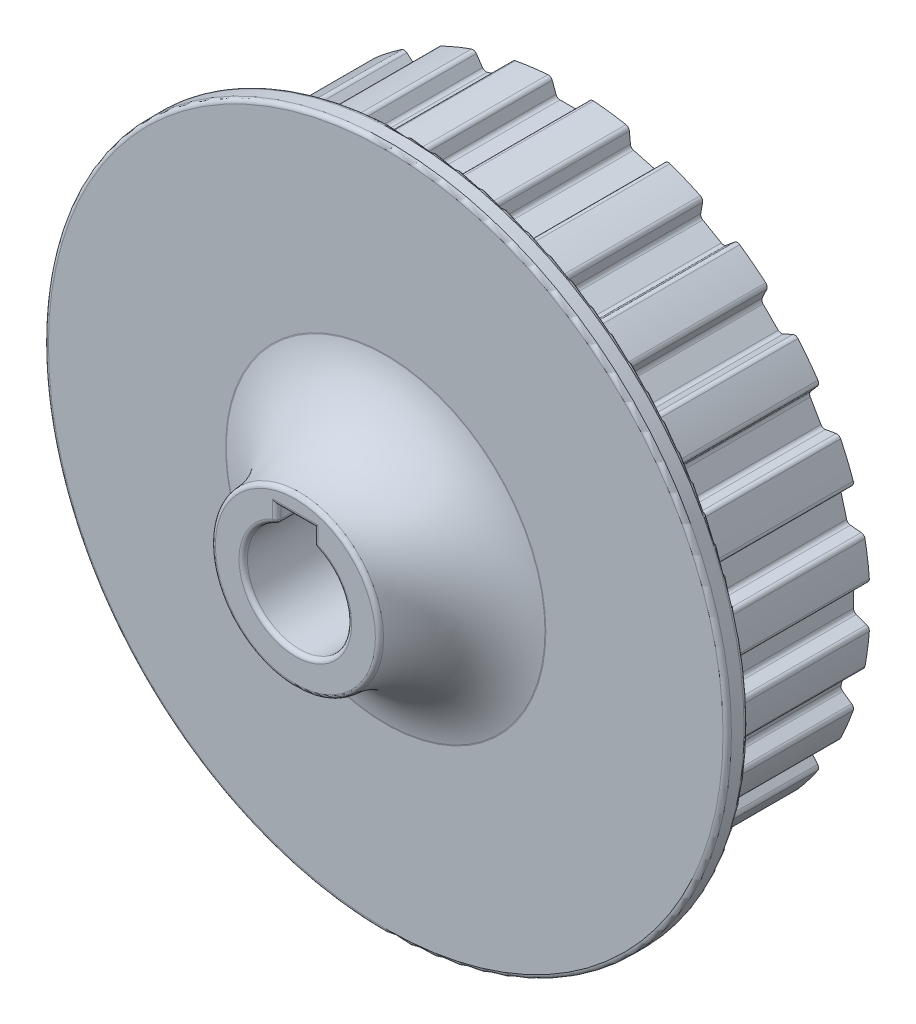
SolidWorks part; units mm, degrees
ref_plane "Front Plane" through (0, 0, 0) normal (0, 0, 1) x (1, 0, 0)
ref_plane "Top Plane" through (0, 0, 0) normal (0, 1, 0) x (1, 0, 0)
ref_plane "Right Plane" through (0, 0, 0) normal (1, 0, 0) x (0, 0, -1)
sketch "Sketch1" plane through (0, 0, 0) normal (0, 1, 0) x (1, 0, 0)
  line L0 (0, 36.1296) -> (0, -19.4741) construction
sketch "Sketch7" plane through (0, 0, 0) normal (0, 0, 1) x (1, 0, 0)
  line L0 (0, 0) -> (0, 34.591) construction
  line L1 (-2.325, 35.546) -> (-2.9401, 37.236) construction
  line L2 (-2.325, 35.546) -> (-1.6298, 33.636) construction
  line L3 (-1.6298, 33.636) -> (1.6298, 33.636) construction
  line L4 (1.6298, 33.636) -> (2.325, 35.546) construction
  line L5 (2.325, 35.546) -> (-2.325, 35.546) construction
  line L6 (0, 33.636) -> (0, 35.546) construction
  line L7 (2.325, 35.546) -> (2.9401, 37.236) construction
  line L8 (-2.9401, 37.236) -> (2.9401, 37.236) construction
  line L9 (0, 0) -> (8.9528, 33.4123) construction
  line L10 (8.9528, 33.4123) -> (9.2196, 34.4082) construction
  line L11 (0, 35.546) -> (0, 35.622) construction
  line L12 (0, 35.622) -> (0, 37.3519) construction
  line L13 (0, 36.4869) -> (9.4435, 35.2437) construction
  line L14 (9.2196, 34.4082) -> (9.6674, 36.0792) construction
  circle A1 centre (0, 0) radius 34.591 construction
  circle A2 centre (-1.2727, 34.146) radius 0.51 construction
  circle A3 centre (1.2727, 34.146) radius 0.51 construction
  circle A4 centre (0, 0) radius 35.622
  circle A5 centre (0, 0) radius 37.3519 construction
  dimension "D3" = 40
  dimension "D6" = 1.02
  dimension "D1" = 3.6
  dimension "D2" = 15
  dimension "D7" = 9.525
  dimension "D4" = 1.91
  dimension "D5" = 4.65
extrude "Boss-Extrude1" add sketch "Sketch7" along normal blind 7.25 and the other way blind 7.25 contours A4 region at (0, 0, 0)
sketch "Sketch14" plane through (0, 0, 0) normal (1, 0, 0) x (0, 0, -1)
  line L0 (-18, 0) -> (-18, 10)
  line L1 (-18, 0) -> (0, 0)
  line L2 (0, 0) -> (0, 19)
  line L3 (0, 19) -> (-7.25, 19)
  line L4 (-7.25, 19) -> (-18, 10)
  line L5 (-7.25, 35.622) -> (-7.25, -35.622) construction
  line L6 (-18, 6.7395) -> (-3.3555, 19) construction
  arc A0 (-7.25, 19) -> (-18, 10) centre (-18.1316, 21.0773) cw
  dimension "D1" = 10
  dimension "D2" = 19
  dimension "D3" = 18
  dimension "D4" = 2.5
revolve "Revolve1" add sketch "Sketch14" angle 360 about L0 region at (0, 7.5733, 7.5341) region at (0, 9.2725, 16.1663) region at (0, 17.2765, 6.6188)
sketch "Sketch9" plane through (0, 0, 0) normal (0, 0, 1) x (1, 0, 0)
  line L0 (2, 0) -> (-2, 0) construction
  line L1 (-2, 0) -> (-2, 7.5) construction
  line L2 (-2, 7.5) -> (2, 7.5) construction
  line L3 (2, 7.5) -> (2, 0) construction
  circle A0 centre (0, 0) radius 6 construction
  dimension "D1" = 12
  dimension "D2" = 4
  dimension "D3" = 7.5
sketch "Sketch10" plane through (0, 0, 0) normal (0, 0, 1) x (1, 0, 0)
  line L0 (2, 0) -> (-2, 0) construction
  line L1 (-2.2, 7.7) -> (2.2, 7.7)
  line L2 (-2.2, 7.7) -> (-2.2, 0)
  line L3 (-2.2, 0) -> (2.2, 0)
  line L4 (2.2, 7.7) -> (2.2, 0)
  line L5 (-2, 7.5) -> (2, 7.5) construction
  line L6 (2, 7.5) -> (2, 0) construction
  circle A0 centre (0, 0) radius 6.2
  circle A1 centre (0, 0) radius 6 construction
  dimension "D1" = 0.2
  dimension "D2" = 0.2
  dimension "D3" = 0.2
extrude "Cut-Extrude3" cut sketch "Sketch10" against normal through all both and the other way through all contours A0 L4 L1 L2 | L2 A0 L4 L3 | L4 A0 L2 L3 region at (0, 6.8793, 0) region at (0, 3.0348, 0) region at (0, -0.8613, 0)
sketch "Sketch11" [suppressed] plane through (0, 0, 0) normal (0, 1, 0) x (1, 0, 0)
  line L0 (29.5757, 7.25) -> (-29.5757, 7.25) construction
  line L1 (11, 7.25) -> (17.5, 7.25)
  line L2 (11, 7.25) -> (11, 4.75)
  line L3 (11, 4.75) -> (17.5, 4.75)
  line L4 (17.5, 7.25) -> (17.5, 4.75)
  line L5 (-29.5757, -7.25) -> (29.5757, -7.25) construction
  line L6 (11, -7.25) -> (17.5, -7.25)
  line L7 (11, -7.25) -> (11, -4.75)
  line L8 (11, -4.75) -> (17.5, -4.75)
  line L9 (17.5, -7.25) -> (17.5, -4.75)
  line L11 (11, 4.75) -> (11, -4.75) construction
  line L12 (17.5, -4.75) -> (17.5, 4.75) construction
  line L13 (6.2, 7.25) -> (-6.2, 7.25) construction
  line L14 (0, 7.25) -> (22.5, 7.25)
  line L15 (0, 7.25) -> (0, -7.25)
  line L16 (0, -7.25) -> (22.5, -7.25)
  line L17 (22.5, 7.25) -> (22.5, -7.25)
  line L18 (-6.2, -7.25) -> (6.2, -7.25) construction
  line L19 (6, 7.25) -> (6, -7.25) construction
  dimension "D1" = 22.5
  dimension "D2" = 6
  dimension "D3" = 5
  dimension "D4" = 5
  dimension "D5" = 2.5
sketch "Sketch15" plane through (0, 0, -7.25) normal (0, 0, -1) x (-1, 0, 0)
  circle A0 centre (0, 0) radius 8.0081
  circle A1 centre (0, 0) radius 2.25
  dimension "D1" = 4.5
extrude "Boss-Extrude2" add sketch "Sketch15" against normal blind 5.5
sketch "Sketch16" plane through (0, 0, -7.25) normal (0, 0, -1) x (-1, 0, 0)
  circle A0 centre (0, 0) radius 5
  dimension "D1" = 10
extrude "Cut-Extrude4" cut sketch "Sketch16" against normal blind 3
sketch "Sketch17" plane through (0, 0, -7.25) normal (0, 0, -1) x (-1, 0, 0)
  circle A0 centre (0, 0) radius 35.622
  circle A1 centre (0, 0) radius 35.622 construction
  circle A2 centre (0, 0) radius 5
  circle A3 centre (0, 0) radius 5 construction
extrude "Boss-Extrude3" add sketch "Sketch17" along normal blind 7.5
sketch "Sketch8" plane through (0, 0, 0) normal (0, 0, 1) x (1, 0, 0)
  line L6 (-1.6298, 33.636) -> (-2.3526, 35.622)
  line L7 (-2.3526, 35.622) -> (2.3526, 35.622)
  line L8 (2.3526, 35.622) -> (1.6298, 33.636)
  line L9 (1.6298, 33.636) -> (-1.6298, 33.636)
  line L10 (-2.325, 35.546) -> (-1.6298, 33.636) construction
  line L11 (1.6298, 33.636) -> (2.325, 35.546) construction
  line L12 (7.1314, 32.9117) -> (6.9472, 35.0171)
  line L13 (6.9472, 35.0171) -> (11.4921, 33.7993)
  line L14 (11.4921, 33.7993) -> (10.2799, 32.0681)
  line L15 (10.2799, 32.0681) -> (7.1314, 32.9117)
  line L16 (15.4065, 29.9445) -> (15.7735, 32.0258)
  line L17 (15.7735, 32.0258) -> (19.8484, 29.6732)
  line L18 (19.8484, 29.6732) -> (18.2295, 28.3147)
  line L19 (18.2295, 28.3147) -> (15.4065, 29.9445)
  line L20 (22.6318, 24.9367) -> (23.525, 26.8521)
  line L21 (23.525, 26.8521) -> (26.8521, 23.525)
  line L22 (26.8521, 23.525) -> (24.9367, 22.6318)
  line L23 (24.9367, 22.6318) -> (22.6318, 24.9367)
  line L24 (28.3147, 18.2295) -> (29.6732, 19.8484)
  line L25 (29.6732, 19.8484) -> (32.0258, 15.7735)
  line L26 (32.0258, 15.7735) -> (29.9445, 15.4065)
  line L27 (29.9445, 15.4065) -> (28.3147, 18.2295)
  line L28 (32.0681, 10.2799) -> (33.7993, 11.4921)
  line L29 (33.7993, 11.4921) -> (35.0171, 6.9472)
  line L30 (35.0171, 6.9472) -> (32.9117, 7.1314)
  line L31 (32.9117, 7.1314) -> (32.0681, 10.2799)
  line L32 (33.636, 1.6298) -> (35.622, 2.3526)
  line L33 (35.622, 2.3526) -> (35.622, -2.3526)
  line L34 (35.622, -2.3526) -> (33.636, -1.6298)
  line L35 (33.636, -1.6298) -> (33.636, 1.6298)
  line L36 (32.9117, -7.1314) -> (35.0171, -6.9472)
  line L37 (35.0171, -6.9472) -> (33.7993, -11.4921)
  line L38 (33.7993, -11.4921) -> (32.0681, -10.2799)
  line L39 (32.0681, -10.2799) -> (32.9117, -7.1314)
  line L40 (29.9445, -15.4065) -> (32.0258, -15.7735)
  line L41 (32.0258, -15.7735) -> (29.6732, -19.8484)
  line L42 (29.6732, -19.8484) -> (28.3147, -18.2295)
  line L43 (28.3147, -18.2295) -> (29.9445, -15.4065)
  line L44 (24.9367, -22.6318) -> (26.8521, -23.525)
  line L45 (26.8521, -23.525) -> (23.525, -26.8521)
  line L46 (23.525, -26.8521) -> (22.6318, -24.9367)
  line L47 (22.6318, -24.9367) -> (24.9367, -22.6318)
  line L48 (18.2295, -28.3147) -> (19.8484, -29.6732)
  line L49 (19.8484, -29.6732) -> (15.7735, -32.0258)
  line L50 (15.7735, -32.0258) -> (15.4065, -29.9445)
  line L51 (15.4065, -29.9445) -> (18.2295, -28.3147)
  line L52 (10.2799, -32.0681) -> (11.4921, -33.7993)
  line L53 (11.4921, -33.7993) -> (6.9472, -35.0171)
  line L54 (6.9472, -35.0171) -> (7.1314, -32.9117)
  line L55 (7.1314, -32.9117) -> (10.2799, -32.0681)
  line L56 (1.6298, -33.636) -> (2.3526, -35.622)
  line L57 (2.3526, -35.622) -> (-2.3526, -35.622)
  line L58 (-2.3526, -35.622) -> (-1.6298, -33.636)
  line L59 (-1.6298, -33.636) -> (1.6298, -33.636)
  line L60 (-7.1314, -32.9117) -> (-6.9472, -35.0171)
  line L61 (-6.9472, -35.0171) -> (-11.4921, -33.7993)
  line L62 (-11.4921, -33.7993) -> (-10.2799, -32.0681)
  line L63 (-10.2799, -32.0681) -> (-7.1314, -32.9117)
  line L64 (-15.4065, -29.9445) -> (-15.7735, -32.0258)
  line L65 (-15.7735, -32.0258) -> (-19.8484, -29.6732)
  line L66 (-19.8484, -29.6732) -> (-18.2295, -28.3147)
  line L67 (-18.2295, -28.3147) -> (-15.4065, -29.9445)
  line L68 (-22.6318, -24.9367) -> (-23.525, -26.8521)
  line L69 (-23.525, -26.8521) -> (-26.8521, -23.525)
  line L70 (-26.8521, -23.525) -> (-24.9367, -22.6318)
  line L71 (-24.9367, -22.6318) -> (-22.6318, -24.9367)
  line L72 (-28.3147, -18.2295) -> (-29.6732, -19.8484)
  line L73 (-29.6732, -19.8484) -> (-32.0258, -15.7735)
  line L74 (-32.0258, -15.7735) -> (-29.9445, -15.4065)
  line L75 (-29.9445, -15.4065) -> (-28.3147, -18.2295)
  line L76 (-32.0681, -10.2799) -> (-33.7993, -11.4921)
  line L77 (-33.7993, -11.4921) -> (-35.0171, -6.9472)
  line L78 (-35.0171, -6.9472) -> (-32.9117, -7.1314)
  line L79 (-32.9117, -7.1314) -> (-32.0681, -10.2799)
  line L80 (-33.636, -1.6298) -> (-35.622, -2.3526)
  line L81 (-35.622, -2.3526) -> (-35.622, 2.3526)
  line L82 (-35.622, 2.3526) -> (-33.636, 1.6298)
  line L83 (-33.636, 1.6298) -> (-33.636, -1.6298)
  line L84 (-32.9117, 7.1314) -> (-35.0171, 6.9472)
  line L85 (-35.0171, 6.9472) -> (-33.7993, 11.4921)
  line L86 (-33.7993, 11.4921) -> (-32.0681, 10.2799)
  line L87 (-32.0681, 10.2799) -> (-32.9117, 7.1314)
  line L88 (-29.9445, 15.4065) -> (-32.0258, 15.7735)
  line L89 (-32.0258, 15.7735) -> (-29.6732, 19.8484)
  line L90 (-29.6732, 19.8484) -> (-28.3147, 18.2295)
  line L91 (-28.3147, 18.2295) -> (-29.9445, 15.4065)
  line L92 (-24.9367, 22.6318) -> (-26.8521, 23.525)
  line L93 (-26.8521, 23.525) -> (-23.525, 26.8521)
  line L94 (-23.525, 26.8521) -> (-22.6318, 24.9367)
  line L95 (-22.6318, 24.9367) -> (-24.9367, 22.6318)
  line L96 (-18.2295, 28.3147) -> (-19.8484, 29.6732)
  line L97 (-19.8484, 29.6732) -> (-15.7735, 32.0258)
  line L98 (-15.7735, 32.0258) -> (-15.4065, 29.9445)
  line L99 (-15.4065, 29.9445) -> (-18.2295, 28.3147)
  line L100 (-10.2799, 32.0681) -> (-11.4921, 33.7993)
  line L101 (-11.4921, 33.7993) -> (-6.9472, 35.0171)
  line L102 (-6.9472, 35.0171) -> (-7.1314, 32.9117)
  line L103 (-7.1314, 32.9117) -> (-10.2799, 32.0681)
  circle A0 centre (0, 0) radius 35.622 construction
  point P119 (0, 0)
  dimension "D1" = 24
extrude "Cut-Extrude2" cut sketch "Sketch8" against normal through all both and the other way through all
fillet "Fillet2" radius 0.51 96 edges at (-19.7865, -29.6212, -3.75) (-15.7595, -31.9462, -3.75) (-11.4458, -33.7331, -3.75) (-6.9542, -34.9366, -3.75) (-2.325, -35.546, -3.75) (2.325, -35.546, -3.75) (6.9542, -34.9366, -3.75) (11.4458, -33.7331, -3.75) (15.7595, -31.9462, -3.75) (19.7865, -29.6212, -3.75) (23.4908, -26.7788, -3.75) (26.7788, -23.4908, -3.75) (29.6212, -19.7865, -3.75) (31.9462, -15.7595, -3.75) (33.7331, -11.4458, -3.75) (34.9366, -6.9542, -3.75) (35.546, -2.325, -3.75) (35.546, 2.325, -3.75) (34.9366, 6.9542, -3.75) (33.7331, 11.4458, -3.75) (31.9462, 15.7595, -3.75) (29.6212, 19.7865, -3.75) (26.7788, 23.4908, -3.75) (23.4908, 26.7788, -3.75) (19.7865, 29.6212, -3.75) (15.7595, 31.9462, -3.75) (11.4458, 33.7331, -3.75) (6.9542, 34.9366, -3.75) (2.325, 35.546, -3.75) (-18.2295, -28.3147, -3.75) (-15.4065, -29.9445, -3.75) (-10.2799, -32.0681, -3.75) (-7.1314, -32.9117, -3.75) (-1.6298, -33.636, -3.75) (1.6298, -33.636, -3.75) (7.1314, -32.9117, -3.75) (10.2799, -32.0681, -3.75) (15.4065, -29.9445, -3.75) (18.2295, -28.3147, -3.75) (22.6318, -24.9367, -3.75) (24.9367, -22.6318, -3.75) (28.3147, -18.2295, -3.75) (29.9445, -15.4065, -3.75) (32.0681, -10.2799, -3.75) (32.9117, -7.1314, -3.75) (33.636, -1.6298, -3.75) (33.636, 1.6298, -3.75) (32.9117, 7.1314, -3.75) (32.0681, 10.2799, -3.75) (29.9445, 15.4065, -3.75) (28.3147, 18.2295, -3.75) (24.9367, 22.6318, -3.75) (22.6318, 24.9367, -3.75) (18.2295, 28.3147, -3.75) (15.4065, 29.9445, -3.75) (10.2799, 32.0681, -3.75) (7.1314, 32.9117, -3.75) (1.6298, 33.636, -3.75) (-1.6298, 33.636, -3.75) (-2.325, 35.546, -3.75) (-33.7331, 11.4458, -3.75) (-32.0681, 10.2799, -3.75) (-32.9117, 7.1314, -3.75) (-34.9366, 6.9542, -3.75) (-35.546, 2.325, -3.75) (-33.636, 1.6298, -3.75) (-33.636, -1.6298, -3.75) (-35.546, -2.325, -3.75) (-34.9366, -6.9542, -3.75) (-32.9117, -7.1314, -3.75) (-32.0681, -10.2799, -3.75) (-33.7331, -11.4458, -3.75) (-31.9462, -15.7595, -3.75) (-29.9445, -15.4065, -3.75) (-28.3147, -18.2295, -3.75) (-29.6212, -19.7865, -3.75) (-26.7788, -23.4908, -3.75) (-24.9367, -22.6318, -3.75) (-22.6318, -24.9367, -3.75) (-23.4908, -26.7788, -3.75) (-31.9462, 15.7595, -3.75) (-29.9445, 15.4065, -3.75) (-28.3147, 18.2295, -3.75) (-29.6212, 19.7865, -3.75) (-26.7788, 23.4908, -3.75) (-24.9367, 22.6318, -3.75) (-22.6318, 24.9367, -3.75) (-23.4908, 26.7788, -3.75) (-19.7865, 29.6212, -3.75) (-18.2295, 28.3147, -3.75) (-15.4065, 29.9445, -3.75) (-15.7595, 31.9462, -3.75) (-11.4458, 33.7331, -3.75) (-10.2799, 32.0681, -3.75) (-7.1314, 32.9117, -3.75) (-6.9542, 34.9366, -3.75)
sketch "Sketch18" plane through (0, 0, -14.75) normal (0, 0, -1) x (-1, 0, 0)
  circle A0 centre (0, 0) radius 5
  circle A1 centre (0, 0) radius 40.622
  circle A2 centre (0, 0) radius 35.622
  circle A3 centre (0, 0) radius 5 construction
  circle A4 centre (0, 0) radius 35.622 construction
  dimension "D1" = 5
extrude "Boss-Extrude4" add sketch "Sketch18" along normal blind 2.5 contours A1 A2 | A2 A0 region at (39.473, 0, -14.75) region at (34.6144, 0, -14.75)
sketch "Sketch19" plane through (0, 0, 7.25) normal (0, 0, 1) x (1, 0, 0)
  circle A0 centre (0, 0) radius 19
  circle A1 centre (0, 0) radius 40.622
  circle A2 centre (0, 0) radius 40.622 construction
  circle A3 centre (0, 0) radius 19 construction
extrude "Boss-Extrude5" add sketch "Sketch19" against normal blind 2.5
sketch "Sketch20" plane through (0, 0, 18) normal (0, 0, 1) x (1, 0, 0)
  line L0 (-2.2, 5.7966) -> (-2.2, 7.7)
  line L1 (-2.2, 7.7) -> (2.2, 7.7)
  line L2 (-2.2, 7.7) -> (2.2, 7.7) construction
  line L3 (2.2, 7.7) -> (2.2, 5.7966)
  circle A0 centre (0, 0) radius 6.2
  arc A1 (-2.2, 5.7966) -> (2.2, 5.7966) centre (0, 0) ccw construction
  arc M2 (2.2, 5.7966) -> (-2.2, 5.7966) centre (0, 0) cw
  line M3 (-2.2, 5.7966) -> (-2.2, 7.7)
  line M4 (-2.2, 7.7) -> (2.2, 7.7)
  line M5 (2.2, 7.7) -> (2.2, 5.7966)
extrude "Cut-Extrude5" cut sketch "Sketch20" against normal through all contours A0 M5 M4 M3 | A0 M2 region at (0, 6.8793, 18) region at (0, 0, 18)
fillet "Fillet3" radius 0.5 12 edges at (2.2, 5.7966, 0.375) (-2.2, 5.7966, 0.375) (2.2, 6.7483, 18) (-2.2, 6.7483, 18) (0, 7.7, 18) (-19, 0, 7.25) (-10, 0, 18) (0, -6.2, 18) (40.622, 0, 4.75) (-40.622, 0, -14.75) (-40.622, 0, -17.25) (40.622, 0, 7.25)
ref_plane "Plane1" through (0, 0, -5.25) normal (0, 0, 1) x (1, 0, 0)
sketch "Sketch21" plane through (0, 0, -5.25) normal (0, 0, 1) x (1, 0, 0)
  circle A0 centre (0, 0) radius 8.0081
  circle A1 centre (0, 0) radius 2.25
  circle A2 centre (0, 0) radius 6.2
  arc A3 (-2.4985, 5.6743) -> (2.4985, 5.6743) centre (0, 0) ccw construction
  dimension "D1" = 4.5
extrude "Boss-Extrude6" add sketch "Sketch21" against normal blind 2.5 contours A2 A1 | A0 A2 region at (-7.7816, 0, -5.25) region at (-6.0246, 0, -5.25)
extrude "Boss-Extrude7" add sketch "Sketch21<4>" against normal up to surface (12 mm away) contours A0 A2 region at (-7.7816, 0, -5.25) up to face at (-40.122, 0, -17.25)
sketch "Sketch21<4>" plane through (0, 0, -5.25) normal (0, 0, 1) x (1, 0, 0) same geometry as "Sketch21"
sketch "Sketch23" plane through (0, 0, -14.75) normal (0, 0, 1) x (1, 0, 0)
  line L0 (0, 33.636) -> (0, 6.2) construction
  line L2 (1.2727, 33.636) -> (-1.2727, 33.636) construction
  circle A0 centre (0, 0) radius 19.918 construction
  circle A1 centre (0, 0) radius 6.2 construction
  circle A2 centre (0, -19.918) radius 1.75
  circle A3 centre (-17.2495, 9.959) radius 1.75
  circle A4 centre (17.2495, 9.959) radius 1.75
  point P10 (0, 19.918)
  point P19 (0, 0)
  point P26 (0, 0)
  dimension "D1" = 3.5
  dimension "D2" = 3
extrude "Cut-Extrude7" cut sketch "Sketch23" against normal through all and the other way blind 10
ref_plane "Plane2" through (0, 0, -12.25) normal (0, 0, 1) x (1, 0, 0)
sketch "Sketch24" plane through (0, 0, -12.25) normal (0, 0, 1) x (1, 0, 0)
  line L0 (0, -19.918) -> (0, 0) construction
  line L1 (-17.2495, 6.6104) -> (-14.3495, 8.2847)
  line L2 (-14.3495, 8.2847) -> (-14.3495, 11.6333)
  line L3 (-14.3495, 11.6333) -> (-17.2495, 13.3076)
  line L4 (-17.2495, 13.3076) -> (-20.1495, 11.6333)
  line L5 (-20.1495, 11.6333) -> (-20.1495, 8.2847)
  line L6 (-20.1495, 8.2847) -> (-17.2495, 6.6104)
  line L7 (2.9, -21.5923) -> (2.9, -18.2437)
  line L8 (2.9, -18.2437) -> (0, -16.5694)
  line L9 (0, -16.5694) -> (-2.9, -18.2437)
  line L10 (-2.9, -18.2437) -> (-2.9, -21.5923)
  line L11 (-2.9, -21.5923) -> (0, -23.2666)
  line L12 (0, -23.2666) -> (2.9, -21.5923)
  line L13 (17.2495, 6.6104) -> (20.1495, 8.2847)
  line L14 (20.1495, 8.2847) -> (20.1495, 11.6333)
  line L15 (20.1495, 11.6333) -> (17.2495, 13.3076)
  line L16 (17.2495, 13.3076) -> (14.3495, 11.6333)
  line L17 (14.3495, 11.6333) -> (14.3495, 8.2847)
  line L18 (14.3495, 8.2847) -> (17.2495, 6.6104)
  line L19 (0, 0) -> (17.2495, 9.959) construction
  line L21 (-17.2495, 9.959) -> (0, 0) construction
  circle A0 centre (-17.2495, 9.959) radius 2.9 construction
  circle A1 centre (0, -19.918) radius 2.9 construction
  circle A2 centre (17.2495, 9.959) radius 2.9 construction
  dimension "D1" = 5.8
extrude "Cut-Extrude8" cut sketch "Sketch24" along normal blind 3 contours L13 L14 L15 L16 | L13 L16 L17 L18 | L3 L4 L5 L6 | L3 L6 L1 L2 | L10 L7 L8 L9 | L10 L11 L12 L7 region at (-17.2495, 9.959, -12.25) region at (0, -19.918, -12.25) region at (17.2495, 9.959, -12.25)
sketch "Sketch25" plane through (0, 0, -9.25) normal (0, 0, -1) x (-1, 0, 0)
  circle A0 centre (0, -19.918) radius 1.75
  circle A1 centre (17.2495, 9.959) radius 1.75
  circle A2 centre (-17.2495, 9.959) radius 1.75
  circle A3 centre (0, -19.918) radius 1.75 construction
extrude "Boss-Extrude8" add sketch "Sketch25" against normal blind 0.2
sketch "Sketch22" plane through (0, 0, 0) normal (0, 1, 0) x (1, 0, 0)
  line L0 (40.622, 15.25) -> (40.622, 16.75) construction
  line L1 (-40.622, 17.25) -> (40.622, 17.25)
  line L2 (-40.622, 17.25) -> (-40.622, 14.75)
  line L3 (-40.622, 14.75) -> (40.622, 14.75)
  line L4 (40.622, 17.25) -> (40.622, 14.75)
  line L5 (-40.622, 17.25) -> (40.622, 14.75) construction
  line L6 (-40.622, 14.75) -> (40.622, 17.25) construction
  line L7 (-32.1547, -18) -> (32.1547, -18) construction
  line L8 (-40.622, 14.75) -> (40.622, 14.75)
  line L9 (-40.622, 14.75) -> (-40.622, -18)
  line L10 (-40.622, -18) -> (40.622, -18)
  line L11 (40.622, 14.75) -> (40.622, -18)
  line L12 (-40.122, 14.75) -> (40.122, 14.75) construction
  line L13 (1.75, 17.25) -> (-1.75, 17.25) construction
  line L14 (-40.622, 16.75) -> (-40.622, 15.25) construction
  point P0 (0, 16)
extrude "Cut-Extrude10" cut sketch "Sketch22" against normal through all both and the other way through all contours L4 L1 L2 L3 region at (0, 0, -16)
